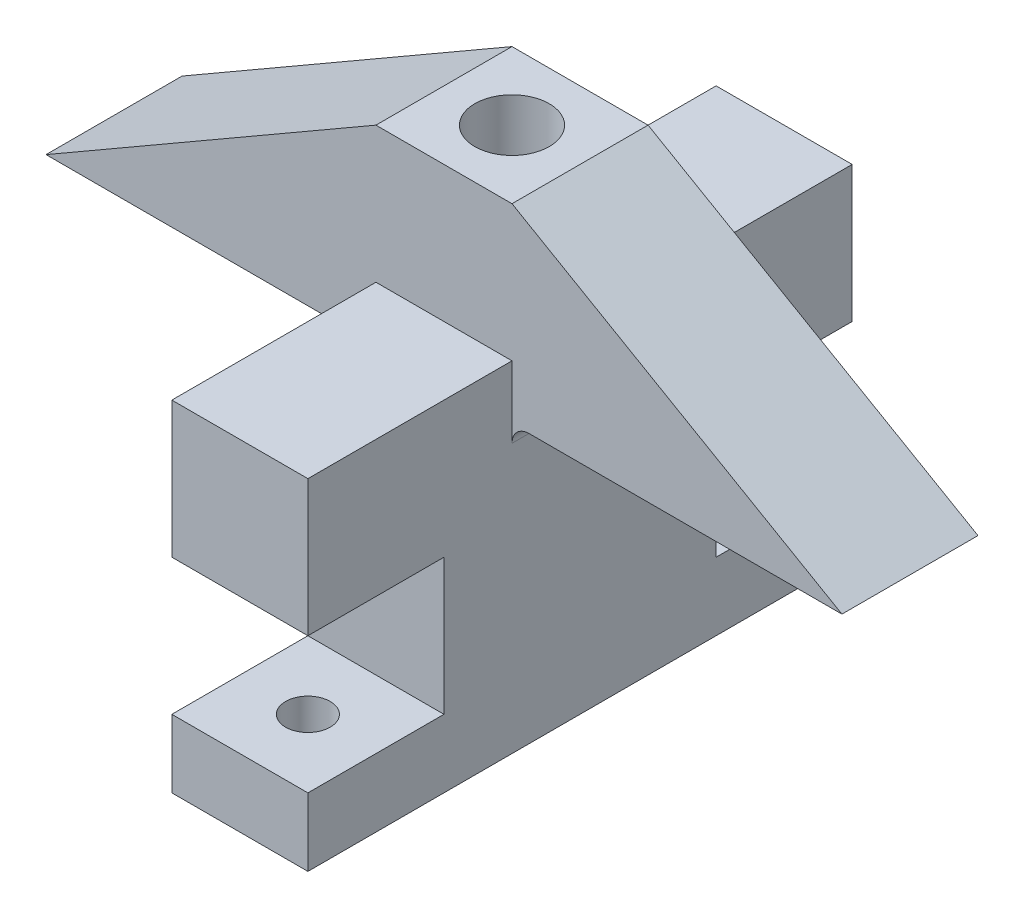
SolidWorks part; units mm, degrees
material "PET"
ref_plane "Front Plane" through (0, 0, 0) normal (0, 0, 1) x (1, 0, 0)
ref_plane "Top Plane" through (0, 0, 0) normal (0, 1, 0) x (1, 0, 0)
ref_plane "Right Plane" through (0, 0, 0) normal (1, 0, 0) x (0, 0, -1)
sketch "Sketch1" plane through (0, 0, 0) normal (0, 0, 1) x (1, 0, 0)
  line L0 (0, 0) -> (0, 53.34)
  line L1 (0, 53.34) -> (-61.5917, 53.34)
  line L2 (-61.5917, 53.34) -> (0, 88.9)
  line L3 (0, 88.9) -> (25.4, 88.9)
  line L4 (25.4, 88.9) -> (86.9917, 53.34)
  line L5 (86.9917, 53.34) -> (25.4, 53.34)
  line L6 (25.4, 53.34) -> (25.4, 0)
  line L7 (25.4, 0) -> (0, 0)
  point P9 (12.7, 88.9)
  point P10 (12.7, 0)
  dimension "D1" = 35.56
  dimension "D2" = 25.4
  dimension "D3" = 30
  dimension "D4" = 30
  dimension "D5" = 25.4
  dimension "D6" = 88.9
extrude "Boss-Extrude1" add sketch "Sketch1" along normal blind 25.4
sketch "Sketch2" plane through (0, 0, 25.4) normal (0, 0, 1) x (1, 0, 0)
  line L1 (0, 0) -> (25.4, 0)
  line L2 (0, 0) -> (0, 12.7)
  line L3 (0, 12.7) -> (25.4, 12.7)
  line L4 (25.4, 0) -> (25.4, 12.7)
  line L5 (25.4, 0) -> (25.4, 53.34) construction
  dimension "D1" = 12.7
extrude "Boss-Extrude2" add sketch "Sketch2" along normal blind 38.1
sketch "Sketch3" plane through (0, 0, 0) normal (0, 0, -1) x (-1, 0, 0)
  line L1 (-25.4, 0) -> (0, 0)
  line L2 (-25.4, 0) -> (-25.4, 12.7)
  line L3 (-25.4, 12.7) -> (0, 12.7)
  line L4 (0, 0) -> (0, 12.7)
  line L5 (0, 53.34) -> (0, 0) construction
  point P5 (0, 0)
  dimension "D1" = 12.7
extrude "Boss-Extrude3" add sketch "Sketch3" along normal blind 38.1
hole_wizard "Ø0.328in Dowel Hole1" positions "Sketch4" profile "Sketch5" hole size "Ø1.0" standard "ISO" end condition through all
sketch "Sketch4" plane through (0, 12.7, 0) normal (0, 1, 0) x (1, 0, 0)
  point P0 (12.7, 25.4)
  point P2 (12.7, -50.8)
  dimension "D1" = 12.7
  dimension "D2" = 12.7
  dimension "D3" = 12.7
  dimension "D4" = 12.7
sketch "Sketch5" plane through (12.7, 12.7, -25.4) normal (1, 0, 0) x (0, 0, 1)
  line L0 (0, 0) -> (0, 12.7)
  line L1 (0, 12.7) -> (4.1656, 12.7)
  line L2 (4.1656, 12.7) -> (4.1656, 0)
  line L5 (4.1656, 0) -> (0, 0)
  line L11 (0, -6.35) -> (0, 107.95) construction
  dimension "Thru Hole Dia." = 8.3312
  dimension "Thru Hole Depth" = 12.7
hole_wizard "Ø0.55in Dowel Hole2" positions "Sketch7" profile "Sketch6" hole size "Ø1.0" standard "ISO"
sketch "Sketch7" plane through (0, 88.9, 0) normal (0, 1, 0) x (1, 0, 0)
  point P0 (12.7, -12.7)
  dimension "D1" = 12.7
  dimension "D2" = 12.7
sketch "Sketch6" plane through (12.7, 88.9, 12.7) normal (1, 0, 0) x (0, 0, 1)
  line L0 (0, 0) -> (0, 39.2261)
  line L1 (0, 39.2261) -> (6.9469, 35.052)
  line L2 (6.9469, 35.052) -> (6.9469, 0)
  line L5 (6.9469, 0) -> (0, 0)
  line L10 (0, 39.2261) -> (-6.9469, 35.052) construction
  line L11 (0, -6.35) -> (0, 107.95) construction
  dimension "Hole Dia." = 13.8938
  dimension "Hole Depth" = 35.052
  dimension "Drill Angle" = 118
fillet "Fillet1" radius 3.175 2 edges at (25.4, 53.34, 12.7) (0, 53.34, 12.7)
sketch "Sketch8" plane through (0, 0, 25.4) normal (0, 0, 1) x (1, 0, 0)
  line L0 (25.4, 12.7) -> (25.4, 50.165) construction
  line L1 (0, 12.7) -> (25.4, 12.7)
  line L2 (0, 12.7) -> (0, 63.5)
  line L3 (0, 63.5) -> (25.4, 63.5)
  line L4 (25.4, 12.7) -> (25.4, 63.5)
  line L5 (0, 38.1) -> (25.4, 38.1)
  line M5 (0, 12.7) -> (25.4, 12.7)
  line M6 (25.4, 12.7) -> (25.4, 50.165)
  line M14 (0, 50.165) -> (0, 12.7)
  dimension "D1" = 50.8
  dimension "D2" = 25.4
extrude "Boss-Extrude4" add sketch "Sketch8" along normal blind 12.7 contours L5 L2 M5 M6 region at (12.7, 25.4, 25.4)
extrude "Boss-Extrude5" add sketch "Sketch8<3>" along normal blind 38.1 contours L5 L4 L3 L2 M14 region at (12.7, 50.8, 25.4)
sketch "Sketch8<3>" plane through (0, 0, 25.4) normal (0, 0, 1) x (1, 0, 0) same geometry as "Sketch8"
sketch "Sketch9" plane through (0, 0, 0) normal (0, 0, -1) x (-1, 0, 0)
  line L0 (-25.4, 38.1) -> (0, 38.1)
  line L1 (-25.4, 12.7) -> (0, 12.7)
  line L2 (-25.4, 12.7) -> (-25.4, 63.5)
  line L3 (-25.4, 63.5) -> (0, 63.5)
  line L4 (0, 12.7) -> (0, 63.5)
  line L5 (0, 38.1) -> (0, 12.7) construction
  point P7 (0, 0)
  line M6 (-25.4, 12.7) -> (0, 12.7)
  line M7 (0, 12.7) -> (0, 50.165)
  line M15 (-25.4, 50.165) -> (-25.4, 12.7)
  dimension "D1" = 25.4
  dimension "D2" = 50.8
extrude "Boss-Extrude6" add sketch "Sketch9" along normal blind 12.7 contours L0 M15 M6 M7 region at (12.7, 25.4, 0)
extrude "Boss-Extrude7" add sketch "Sketch9<3>" along normal blind 38.1 contours L4 L3 L2 L0 M7 M15 region at (12.7, 50.8, 0)
sketch "Sketch9<3>" plane through (0, 0, 0) normal (0, 0, -1) x (-1, 0, 0) same geometry as "Sketch9"
